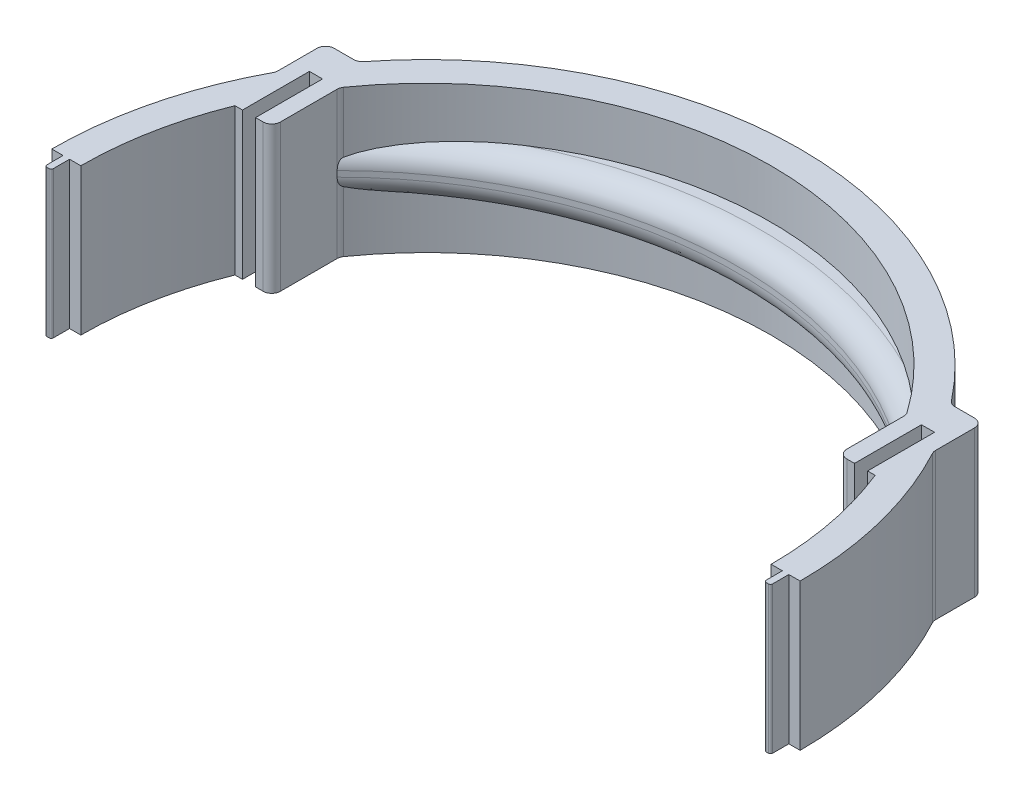
SolidWorks part; units mm, degrees
ref_plane "Front Plane" through (0, 0, 0) normal (0, 0, 1) x (1, 0, 0)
ref_plane "Top Plane" through (0, 0, 0) normal (0, 1, 0) x (1, 0, 0)
ref_plane "Right Plane" through (0, 0, 0) normal (1, 0, 0) x (0, 0, -1)
sketch "Construction Sketch" plane through (0, 0, 0) normal (0, 1, 0) x (1, 0, 0)
  line L0 (-39.5715, 0) -> (39.5715, 0) construction
  line L1 (0, -30.25) -> (0, 30.25) construction
  line L2 (34.71, 22.7218) -> (34.71, 7.2)
  line L3 (-36.21, 22.7218) -> (-34.71, 22.7218)
  line L4 (-36.21, 22.7218) -> (-36.21, 7.2)
  line L5 (-36.21, 7.2) -> (-34.71, 7.2)
  line L6 (-34.71, 22.7218) -> (-34.71, 7.2)
  line L7 (36.21, 7.2) -> (34.71, 7.2)
  line L8 (36.21, 22.7218) -> (36.21, 7.2)
  line L9 (36.21, 22.7218) -> (34.71, 22.7218)
  line L10 (36.21, -22.7218) -> (34.71, -22.7218)
  line L11 (36.21, -22.7218) -> (36.21, -7.2)
  line L12 (36.21, -7.2) -> (34.71, -7.2)
  line L13 (-34.71, -22.7218) -> (-34.71, -7.2)
  line L14 (-36.21, -7.2) -> (-34.71, -7.2)
  line L15 (-36.21, -22.7218) -> (-36.21, -7.2)
  line L16 (-36.21, -22.7218) -> (-34.71, -22.7218)
  line L17 (34.71, -22.7218) -> (34.71, -7.2)
  line L18 (-27.6094, 14.9609) -> (-42.4545, 14.9609) construction
  line L19 (27.6094, 14.9609) -> (42.4545, 14.9609) construction
  line L20 (27.6094, -14.9609) -> (42.4545, -14.9609) construction
  line L21 (-27.6094, -14.9609) -> (-42.4545, -14.9609) construction
  circle A1 centre (0, 0) radius 42.8625
  point P4 (0, 0)
  point P8 (0, 0)
  dimension "D5" = 7.7609
  dimension "D1" = 1.5
  dimension "D2" = 15.5218
  dimension "D3" = 7.2
  dimension "D4" = 34.71
sketch "Sketch3" plane through (0, 0, 0) normal (0, 1, 0) x (1, 0, 0)
  line L0 (-45.7552, 0) -> (45.7552, 0) construction
  line L1 (0, -18.4364) -> (0, 18.4364) construction
  line L2 (34.71, 22.7218) -> (34.71, 14.9609)
  line L3 (-36.23, 22.7218) -> (-34.71, 22.7218)
  line L4 (-36.23, 22.7218) -> (-36.23, 14.9609)
  line L6 (-34.71, 22.7218) -> (-34.71, 14.9609)
  line L8 (36.23, 22.7218) -> (36.23, 14.9609)
  line L9 (36.23, 22.7218) -> (34.71, 22.7218)
  line L10 (36.23, -22.7218) -> (34.71, -22.7218)
  line L11 (36.23, -22.7218) -> (36.23, -14.9609)
  line L13 (-34.71, -22.7218) -> (-34.71, -14.9609)
  line L15 (-36.23, -22.7218) -> (-36.23, -14.9609)
  line L16 (-36.23, -22.7218) -> (-34.71, -22.7218)
  line L17 (34.71, -22.7218) -> (34.71, -14.9609)
  line L18 (-34.8431, 26.4718) -> (-37.105, 26.4718)
  line L19 (-36.23, -14.9609) -> (-37.1022, -14.9609)
  line L21 (36.23, -14.9609) -> (37.1022, -14.9609)
  line L26 (-32.8325, 22.5407) -> (-32.8325, 15.9609)
  line L27 (-42.8625, 33.6264) -> (-42.8625, -34.8883) construction
  line L28 (-33.8325, 14.9609) -> (-34.71, 14.9609)
  line L29 (36.23, 14.9609) -> (37.1022, 14.9609)
  line L31 (-38.105, 25.4718) -> (-38.105, 20.9652)
  line L32 (38.105, 25.4718) -> (38.105, 20.9652)
  line L33 (34.8431, 26.4718) -> (37.105, 26.4718)
  line L34 (33.8325, 14.9609) -> (34.71, 14.9609)
  line L35 (32.8325, 22.5407) -> (32.8325, 15.9609)
  line L36 (38.105, -25.4718) -> (38.105, -20.9652)
  line L37 (34.8431, -26.4718) -> (37.105, -26.4718)
  line L38 (32.8325, -22.5407) -> (32.8325, -15.9609)
  line L39 (33.8325, -14.9609) -> (34.71, -14.9609)
  line L40 (-34.8431, -26.4718) -> (-37.105, -26.4718)
  line L41 (-38.105, -25.4718) -> (-38.105, -20.9652)
  line L42 (-32.8325, -22.5407) -> (-32.8325, -15.9609)
  line L43 (-33.8325, -14.9609) -> (-34.71, -14.9609)
  line L44 (-36.23, 14.9609) -> (-37.1022, 14.9609)
  arc A0 (30.6125, -30.0011) -> (42.8625, 0) centre (0, 0) ccw construction
  arc A1 (-38.2237, 20.4927) -> (-38.2237, -20.4927) centre (0, 0) ccw
  arc A2 (-37.1022, 14.9609) -> (-37.1022, -14.9609) centre (0, 0) ccw
  arc A3 (32.6486, 23.1186) -> (-32.6486, 23.1186) centre (0, 0) ccw
  arc A4 (34.0578, 26.8526) -> (-34.0578, 26.8526) centre (0, 0) ccw
  arc A5 (-32.6486, -23.1186) -> (32.6486, -23.1186) centre (0, 0) ccw
  arc A6 (-34.0578, -26.8526) -> (34.0578, -26.8526) centre (0, 0) ccw
  arc A7 (37.1022, -14.9609) -> (37.1022, 14.9609) centre (0, 0) ccw
  arc A8 (38.2237, -20.4927) -> (38.2237, 20.4927) centre (0, 0) ccw
  arc A9 (-38.105, 20.9652) -> (-38.2237, 20.4927) centre (-39.105, 20.9652) cw
  arc A10 (-34.8431, 26.4718) -> (-34.0578, 26.8526) centre (-34.8431, 27.4718) ccw
  arc A11 (-37.105, 26.4718) -> (-38.105, 25.4718) centre (-37.105, 25.4718) ccw
  arc A12 (-33.8325, 14.9609) -> (-32.8325, 15.9609) centre (-33.8325, 15.9609) ccw
  arc A13 (38.105, 20.9652) -> (38.2237, 20.4927) centre (39.105, 20.9652) ccw
  arc A14 (34.8431, 26.4718) -> (34.0578, 26.8526) centre (34.8431, 27.4718) cw
  arc A15 (-32.6486, -23.1186) -> (-32.8325, -22.5407) centre (-31.8325, -22.5407) cw
  arc A16 (-32.8325, -15.9609) -> (-33.8325, -14.9609) centre (-33.8325, -15.9609) ccw
  arc A17 (-38.105, -20.9652) -> (-38.2237, -20.4927) centre (-39.105, -20.9652) ccw
  arc A18 (-37.105, -26.4718) -> (-38.105, -25.4718) centre (-37.105, -25.4718) cw
  arc A19 (-34.8431, -26.4718) -> (-34.0578, -26.8526) centre (-34.8431, -27.4718) cw
  arc A20 (38.105, -20.9652) -> (38.2237, -20.4927) centre (39.105, -20.9652) cw
  arc A21 (34.8431, -26.4718) -> (34.0578, -26.8526) centre (34.8431, -27.4718) ccw
  arc A22 (32.6486, -23.1186) -> (32.8325, -22.5407) centre (31.8325, -22.5407) ccw
  arc A23 (-32.8325, 22.5407) -> (-32.6486, 23.1186) centre (-31.8325, 22.5407) cw
  arc A24 (38.105, -25.4718) -> (37.105, -26.4718) centre (37.105, -25.4718) cw
  arc A25 (32.8325, -15.9609) -> (33.8325, -14.9609) centre (33.8325, -15.9609) cw
  arc A26 (32.8325, 22.5407) -> (32.6486, 23.1186) centre (31.8325, 22.5407) ccw
  arc A27 (33.8325, 14.9609) -> (32.8325, 15.9609) centre (33.8325, 15.9609) cw
  arc A28 (38.105, 25.4718) -> (37.105, 26.4718) centre (37.105, 25.4718) ccw
  point P3 (0, 0)
  point P6 (0, 0)
  point P54 (-38.105, 20.7125)
  point P57 (-34.3547, 26.4718)
  point P60 (-38.105, 26.4718)
  point P63 (-32.8325, 14.9609)
  point P66 (38.105, 20.7125)
  point P69 (34.3547, 26.4718)
  point P74 (-32.8325, -14.9609)
  point P77 (-38.105, -20.7125)
  point P80 (-38.105, -26.4718)
  point P83 (-34.3547, -26.4718)
  point P86 (38.105, -20.7125)
  point P89 (34.3547, -26.4718)
  point P96 (38.105, -26.4718)
  point P99 (32.8325, -14.9609)
  point P102 (32.8325, 22.8567)
  point P105 (32.8325, 14.9609)
  point P108 (38.105, 26.4718)
  dimension "D3" = 80.01
  dimension "D6" = 7.7609
  dimension "D5" = 86.741
  dimension "D10" = 1
  dimension "D11" = 1
  dimension "D1" = 1.52
  dimension "D2" = 10.03
  dimension "D4" = 34.71
  dimension "D7" = 3.75
  dimension "D8" = 1.875
  dimension "D9" = 8.1525
extrude "Boss-Extrude1" add sketch "Sketch3" along normal blind 5.6667 contours L36 A8 L32 L33 A4 L18 L31 A1 L27 L41 L40 A6 L37 A7 L21 L11 L10 L17 L39 L38 A5 L42 L43 L13 L16 L15 L19 A2 L44 L4 L3 L6 L28 L26 A3 L35 L34 L2 L9 L8 L29
sketch "Sketch4" plane through (0, 5.6667, 0) normal (0, 1, 0) x (1, 0, 0)
  line L0 (-32.8325, 22.5407) -> (-32.8325, 15.9609) construction
  line L1 (-34.71, 22.7218) -> (-34.71, 14.9609) construction
  line L2 (-33.8325, 14.9609) -> (-34.71, 14.9609) construction
  line L3 (-36.23, 22.7218) -> (-34.71, 22.7218) construction
  line L4 (-36.23, 22.7218) -> (-36.23, 14.9609) construction
  line L5 (-36.23, 14.9609) -> (-37.1022, 14.9609) construction
  line L6 (-36.23, -22.7218) -> (-36.23, -14.9609) construction
  line L7 (-36.23, -14.9609) -> (-37.1022, -14.9609) construction
  line L8 (38.105, 20.9652) -> (38.105, 25.4718)
  line L9 (37.105, 26.4718) -> (34.8431, 26.4718)
  line L10 (-34.8431, 26.4718) -> (-37.105, 26.4718)
  line L11 (-38.105, 25.4718) -> (-38.105, 20.9652)
  line L12 (-38.105, -20.9652) -> (-38.105, -25.4718)
  line L13 (-37.105, -26.4718) -> (-34.8431, -26.4718)
  line L14 (34.8431, -26.4718) -> (37.105, -26.4718)
  line L15 (38.105, -25.4718) -> (38.105, -20.9652)
  line L16 (38.105, 20.9652) -> (38.105, 25.4718)
  line L17 (37.105, 26.4718) -> (34.8431, 26.4718)
  line L18 (-34.8431, 26.4718) -> (-37.105, 26.4718)
  line L19 (-38.105, 25.4718) -> (-38.105, 20.9652)
  line L20 (-38.105, -20.9652) -> (-38.105, -25.4718)
  line L21 (-37.105, -26.4718) -> (-34.8431, -26.4718)
  line L22 (34.8431, -26.4718) -> (37.105, -26.4718)
  line L23 (38.105, -25.4718) -> (38.105, -20.9652)
  line L24 (-33.8325, -14.9609) -> (-34.71, -14.9609) construction
  line L25 (-34.71, -22.7218) -> (-34.71, -14.9609) construction
  line L26 (-32.8325, -22.5407) -> (-32.8325, -15.9609) construction
  line L27 (-36.23, -22.7218) -> (-34.71, -22.7218) construction
  line L28 (32.8325, -22.5407) -> (32.8325, -15.9609) construction
  line L29 (34.71, -22.7218) -> (34.71, -14.9609) construction
  line L30 (36.23, -22.7218) -> (34.71, -22.7218) construction
  line L31 (36.23, -22.7218) -> (36.23, -14.9609) construction
  line L32 (33.8325, -14.9609) -> (34.71, -14.9609) construction
  line L33 (36.23, -14.9609) -> (37.1022, -14.9609) construction
  line L34 (36.23, 22.7218) -> (34.71, 22.7218) construction
  line L35 (36.23, 22.7218) -> (36.23, 14.9609) construction
  line L36 (34.71, 22.7218) -> (34.71, 14.9609) construction
  line L37 (32.8325, 22.5407) -> (32.8325, 15.9609) construction
  line L38 (33.8325, 14.9609) -> (34.71, 14.9609) construction
  line L39 (36.23, 14.9609) -> (37.1022, 14.9609) construction
  line L40 (36.23, 14.9609) -> (37.1022, 14.9609)
  line L41 (33.8325, 14.9609) -> (34.71, 14.9609)
  line L42 (32.8325, 22.5407) -> (32.8325, 15.9609)
  line L43 (34.71, 22.7218) -> (34.71, 14.9609)
  line L44 (36.23, 22.7218) -> (36.23, 14.9609)
  line L45 (36.23, 22.7218) -> (34.71, 22.7218)
  line L46 (36.23, -14.9609) -> (37.1022, -14.9609)
  line L47 (33.8325, -14.9609) -> (34.71, -14.9609)
  line L48 (36.23, -22.7218) -> (36.23, -14.9609)
  line L49 (36.23, -22.7218) -> (34.71, -22.7218)
  line L50 (34.71, -22.7218) -> (34.71, -14.9609)
  line L51 (32.8325, -22.5407) -> (32.8325, -15.9609)
  line L52 (-36.23, -22.7218) -> (-34.71, -22.7218)
  line L53 (-32.8325, -22.5407) -> (-32.8325, -15.9609)
  line L54 (-34.71, -22.7218) -> (-34.71, -14.9609)
  line L55 (-33.8325, -14.9609) -> (-34.71, -14.9609)
  line L56 (-36.23, -14.9609) -> (-37.1022, -14.9609)
  line L57 (-36.23, -22.7218) -> (-36.23, -14.9609)
  line L58 (-36.23, 14.9609) -> (-37.1022, 14.9609)
  line L59 (-36.23, 22.7218) -> (-36.23, 14.9609)
  line L60 (-36.23, 22.7218) -> (-34.71, 22.7218)
  line L61 (-33.8325, 14.9609) -> (-34.71, 14.9609)
  line L62 (-34.71, 22.7218) -> (-34.71, 14.9609)
  line L63 (-32.8325, 22.5407) -> (-32.8325, 15.9609)
  arc A1 (32.6486, 23.1186) -> (-32.6486, 23.1186) centre (0, 0) ccw construction
  arc A2 (-32.6486, 23.1186) -> (-32.8325, 22.5407) centre (-31.8325, 22.5407) ccw construction
  arc A3 (-33.8325, 14.9609) -> (-32.8325, 15.9609) centre (-33.8325, 15.9609) ccw construction
  arc A13 (32.8325, 22.5407) -> (32.6486, 23.1186) centre (31.8325, 22.5407) ccw
  arc A14 (32.8325, 15.9609) -> (33.8325, 14.9609) centre (33.8325, 15.9609) ccw
  arc A15 (37.1022, -14.9609) -> (37.1022, 14.9609) centre (0, 0) ccw
  arc A16 (38.105, 25.4718) -> (37.105, 26.4718) centre (37.105, 25.4718) ccw
  arc A17 (34.0578, 26.8526) -> (34.8431, 26.4718) centre (34.8431, 27.4718) ccw
  arc A18 (34.0578, 26.8526) -> (-34.0578, 26.8526) centre (0, 0) ccw
  arc A19 (-34.8431, 26.4718) -> (-34.0578, 26.8526) centre (-34.8431, 27.4718) ccw
  arc A20 (-37.105, 26.4718) -> (-38.105, 25.4718) centre (-37.105, 25.4718) ccw
  arc A21 (-38.2237, 20.4927) -> (-38.105, 20.9652) centre (-39.105, 20.9652) ccw
  arc A22 (-38.2237, 20.4927) -> (-38.2237, -20.4927) centre (0, 0) ccw
  arc A23 (-38.105, -20.9652) -> (-38.2237, -20.4927) centre (-39.105, -20.9652) ccw
  arc A24 (-38.105, -25.4718) -> (-37.105, -26.4718) centre (-37.105, -25.4718) ccw
  arc A25 (-34.0578, -26.8526) -> (-34.8431, -26.4718) centre (-34.8431, -27.4718) ccw
  arc A26 (-34.0578, -26.8526) -> (34.0578, -26.8526) centre (0, 0) ccw
  arc A27 (34.8431, -26.4718) -> (34.0578, -26.8526) centre (34.8431, -27.4718) ccw
  arc A28 (37.105, -26.4718) -> (38.105, -25.4718) centre (37.105, -25.4718) ccw
  arc A29 (38.2237, -20.4927) -> (38.105, -20.9652) centre (39.105, -20.9652) ccw
  arc A30 (38.2237, -20.4927) -> (38.2237, 20.4927) centre (0, 0) ccw
  arc A31 (38.105, 20.9652) -> (38.2237, 20.4927) centre (39.105, 20.9652) ccw
  arc A32 (38.105, 25.4718) -> (37.105, 26.4718) centre (37.105, 25.4718) ccw
  arc A33 (34.0578, 26.8526) -> (34.8431, 26.4718) centre (34.8431, 27.4718) ccw
  arc A34 (34.0578, 26.8526) -> (-34.0578, 26.8526) centre (0, 0) ccw
  arc A35 (-34.8431, 26.4718) -> (-34.0578, 26.8526) centre (-34.8431, 27.4718) ccw
  arc A36 (-37.105, 26.4718) -> (-38.105, 25.4718) centre (-37.105, 25.4718) ccw
  arc A37 (-38.2237, 20.4927) -> (-38.105, 20.9652) centre (-39.105, 20.9652) ccw
  arc A38 (-38.2237, 20.4927) -> (-38.2237, -20.4927) centre (0, 0) ccw
  arc A39 (-38.105, -20.9652) -> (-38.2237, -20.4927) centre (-39.105, -20.9652) ccw
  arc A40 (-38.105, -25.4718) -> (-37.105, -26.4718) centre (-37.105, -25.4718) ccw
  arc A41 (-34.0578, -26.8526) -> (-34.8431, -26.4718) centre (-34.8431, -27.4718) ccw
  arc A42 (-34.0578, -26.8526) -> (34.0578, -26.8526) centre (0, 0) ccw
  arc A43 (34.8431, -26.4718) -> (34.0578, -26.8526) centre (34.8431, -27.4718) ccw
  arc A44 (37.105, -26.4718) -> (38.105, -25.4718) centre (37.105, -25.4718) ccw
  arc A45 (38.2237, -20.4927) -> (38.105, -20.9652) centre (39.105, -20.9652) ccw
  arc A46 (38.2237, -20.4927) -> (38.2237, 20.4927) centre (0, 0) ccw
  arc A47 (38.105, 20.9652) -> (38.2237, 20.4927) centre (39.105, 20.9652) ccw
  arc A48 (33.8325, -14.9609) -> (32.8325, -15.9609) centre (33.8325, -15.9609) ccw
  arc A49 (32.6486, -23.1186) -> (32.8325, -22.5407) centre (31.8325, -22.5407) ccw
  arc A50 (-32.6486, -23.1186) -> (32.6486, -23.1186) centre (0, 0) ccw
  arc A51 (-32.8325, -22.5407) -> (-32.6486, -23.1186) centre (-31.8325, -22.5407) ccw
  arc A52 (-32.8325, -15.9609) -> (-33.8325, -14.9609) centre (-33.8325, -15.9609) ccw
  arc A53 (-37.1022, 14.9609) -> (-37.1022, -14.9609) centre (0, 0) ccw
  arc A54 (-33.8325, 14.9609) -> (-32.8325, 15.9609) centre (-33.8325, 15.9609) ccw
  arc A55 (-32.6486, 23.1186) -> (-32.8325, 22.5407) centre (-31.8325, 22.5407) ccw
  arc A56 (32.6486, 23.1186) -> (-32.6486, 23.1186) centre (0, 0) ccw
  dimension "D1" = 0
ref_plane "Plane1" through (0, 11.3333, 0) normal (0, 1, 0) x (1, 0, 0)
sketch "Sketch5" plane through (0, 11.3333, 0) normal (0, 1, 0) x (1, 0, 0)
  line L0 (38.105, 20.9652) -> (38.105, 25.4718)
  line L1 (37.105, 26.4718) -> (34.8431, 26.4718)
  line L2 (-34.8431, 26.4718) -> (-37.105, 26.4718)
  line L3 (-38.105, 25.4718) -> (-38.105, 20.9652)
  line L4 (-38.105, -20.9652) -> (-38.105, -25.4718)
  line L5 (-37.105, -26.4718) -> (-34.8431, -26.4718)
  line L6 (34.8431, -26.4718) -> (37.105, -26.4718)
  line L7 (38.105, -25.4718) -> (38.105, -20.9652)
  line L8 (36.23, 14.9609) -> (37.1022, 14.9609)
  line L9 (33.8325, 14.9609) -> (34.71, 14.9609)
  line L10 (32.8325, 22.5407) -> (32.8325, 15.9609)
  line L11 (34.71, 22.7218) -> (34.71, 14.9609)
  line L12 (36.23, 22.7218) -> (36.23, 14.9609)
  line L13 (36.23, 22.7218) -> (34.71, 22.7218)
  line L14 (36.23, -14.9609) -> (37.1022, -14.9609)
  line L15 (33.8325, -14.9609) -> (34.71, -14.9609)
  line L16 (36.23, -22.7218) -> (36.23, -14.9609)
  line L17 (36.23, -22.7218) -> (34.71, -22.7218)
  line L18 (34.71, -22.7218) -> (34.71, -14.9609)
  line L19 (32.8325, -22.5407) -> (32.8325, -15.9609)
  line L20 (-36.23, -22.7218) -> (-34.71, -22.7218)
  line L21 (-32.8325, -22.5407) -> (-32.8325, -15.9609)
  line L22 (-34.71, -22.7218) -> (-34.71, -14.9609)
  line L23 (-33.8325, -14.9609) -> (-34.71, -14.9609)
  line L24 (-36.23, -14.9609) -> (-37.1022, -14.9609)
  line L25 (-36.23, -22.7218) -> (-36.23, -14.9609)
  line L26 (-36.23, 14.9609) -> (-37.1022, 14.9609)
  line L27 (-36.23, 22.7218) -> (-36.23, 14.9609)
  line L28 (-36.23, 22.7218) -> (-34.71, 22.7218)
  line L29 (-33.8325, 14.9609) -> (-34.71, 14.9609)
  line L30 (-34.71, 22.7218) -> (-34.71, 14.9609)
  line L31 (-32.8325, 22.5407) -> (-32.8325, 15.9609)
  line L32 (-76.2008, 0) -> (76.2008, 0) construction
  arc A1 (32.8325, 15.9609) -> (33.8325, 14.9609) centre (33.8325, 15.9609) ccw
  arc A2 (37.1022, -14.9609) -> (37.1022, 14.9609) centre (0, 0) ccw
  arc A3 (38.105, 25.4718) -> (37.105, 26.4718) centre (37.105, 25.4718) ccw
  arc A7 (-37.105, 26.4718) -> (-38.105, 25.4718) centre (-37.105, 25.4718) ccw
  arc A8 (-38.2237, 20.4927) -> (-38.105, 20.9652) centre (-39.105, 20.9652) ccw
  arc A9 (-38.2237, 20.4927) -> (-38.2237, -20.4927) centre (0, 0) ccw
  arc A10 (-38.105, -20.9652) -> (-38.2237, -20.4927) centre (-39.105, -20.9652) ccw
  arc A11 (-38.105, -25.4718) -> (-37.105, -26.4718) centre (-37.105, -25.4718) ccw
  arc A15 (37.105, -26.4718) -> (38.105, -25.4718) centre (37.105, -25.4718) ccw
  arc A16 (38.2237, -20.4927) -> (38.105, -20.9652) centre (39.105, -20.9652) ccw
  arc A17 (38.2237, -20.4927) -> (38.2237, 20.4927) centre (0, 0) ccw
  arc A18 (38.105, 20.9652) -> (38.2237, 20.4927) centre (39.105, 20.9652) ccw
  arc A19 (33.8325, -14.9609) -> (32.8325, -15.9609) centre (33.8325, -15.9609) ccw
  arc A23 (-32.8325, -15.9609) -> (-33.8325, -14.9609) centre (-33.8325, -15.9609) ccw
  arc A24 (-37.1022, 14.9609) -> (-37.1022, -14.9609) centre (0, 0) ccw
  arc A25 (-33.8325, 14.9609) -> (-32.8325, 15.9609) centre (-33.8325, 15.9609) ccw
  arc A28 (-32.8325, 22.5407) -> (32.8325, 22.5407) centre (0, -10.2918) cw
  arc A29 (-32.8325, -22.5407) -> (32.8325, -22.5407) centre (0, 10.2918) ccw
  arc A30 (-34.8431, 26.4718) -> (34.8431, 26.4718) centre (0, -8.3713) cw
  arc A31 (-34.8431, -26.4718) -> (34.8431, -26.4718) centre (0, 8.3713) ccw
  point P87 (0, 0)
extrude "Boss-Extrude3" add sketch "Sketch5" against normal blind 5.6667
sketch "Sketch7" plane through (0, 11.3333, 0) normal (0, 1, 0) x (1, 0, 0)
  line L0 (38.105, 20.9652) -> (38.105, 25.4718)
  line L1 (37.105, 26.4718) -> (34.8431, 26.4718)
  line L2 (-34.8431, 26.4718) -> (-37.105, 26.4718)
  line L3 (-38.105, 25.4718) -> (-38.105, 20.9652)
  line L4 (-38.105, -20.9652) -> (-38.105, -25.4718)
  line L5 (-37.105, -26.4718) -> (-34.8431, -26.4718)
  line L6 (34.8431, -26.4718) -> (37.105, -26.4718)
  line L7 (38.105, -25.4718) -> (38.105, -20.9652)
  line L8 (36.23, 14.9609) -> (37.1022, 14.9609)
  line L9 (33.8325, 14.9609) -> (34.71, 14.9609)
  line L10 (32.8325, 22.5407) -> (32.8325, 15.9609)
  line L11 (34.71, 22.7218) -> (34.71, 14.9609)
  line L12 (36.23, 22.7218) -> (36.23, 14.9609)
  line L13 (36.23, 22.7218) -> (34.71, 22.7218)
  line L14 (36.23, -14.9609) -> (37.1022, -14.9609)
  line L15 (33.8325, -14.9609) -> (34.71, -14.9609)
  line L16 (36.23, -22.7218) -> (36.23, -14.9609)
  line L17 (36.23, -22.7218) -> (34.71, -22.7218)
  line L18 (34.71, -22.7218) -> (34.71, -14.9609)
  line L19 (32.8325, -22.5407) -> (32.8325, -15.9609)
  line L20 (-36.23, -22.7218) -> (-34.71, -22.7218)
  line L21 (-32.8325, -22.5407) -> (-32.8325, -15.9609)
  line L22 (-34.71, -22.7218) -> (-34.71, -14.9609)
  line L23 (-33.8325, -14.9609) -> (-34.71, -14.9609)
  line L24 (-36.23, -14.9609) -> (-37.1022, -14.9609)
  line L25 (-36.23, -22.7218) -> (-36.23, -14.9609)
  line L26 (-36.23, 14.9609) -> (-37.1022, 14.9609)
  line L27 (-36.23, 22.7218) -> (-36.23, 14.9609)
  line L28 (-36.23, 22.7218) -> (-34.71, 22.7218)
  line L29 (-33.8325, 14.9609) -> (-34.71, 14.9609)
  line L30 (-34.71, 22.7218) -> (-34.71, 14.9609)
  line L31 (-32.8325, 22.5407) -> (-32.8325, 15.9609)
  arc A0 (32.8325, 22.5407) -> (32.6486, 23.1186) centre (31.8325, 22.5407) ccw
  arc A1 (32.8325, 15.9609) -> (33.8325, 14.9609) centre (33.8325, 15.9609) ccw
  arc A2 (37.1022, -14.9609) -> (37.1022, 14.9609) centre (0, 0) ccw
  arc A3 (38.105, 25.4718) -> (37.105, 26.4718) centre (37.105, 25.4718) ccw
  arc A4 (34.0578, 26.8526) -> (34.8431, 26.4718) centre (34.8431, 27.4718) ccw
  arc A5 (34.0578, 26.8526) -> (-34.0578, 26.8526) centre (0, 0) ccw
  arc A6 (-34.8431, 26.4718) -> (-34.0578, 26.8526) centre (-34.8431, 27.4718) ccw
  arc A7 (-37.105, 26.4718) -> (-38.105, 25.4718) centre (-37.105, 25.4718) ccw
  arc A8 (-38.2237, 20.4927) -> (-38.105, 20.9652) centre (-39.105, 20.9652) ccw
  arc A9 (-38.2237, 20.4927) -> (-38.2237, -20.4927) centre (0, 0) ccw
  arc A10 (-38.105, -20.9652) -> (-38.2237, -20.4927) centre (-39.105, -20.9652) ccw
  arc A11 (-38.105, -25.4718) -> (-37.105, -26.4718) centre (-37.105, -25.4718) ccw
  arc A12 (-34.0578, -26.8526) -> (-34.8431, -26.4718) centre (-34.8431, -27.4718) ccw
  arc A13 (-34.0578, -26.8526) -> (34.0578, -26.8526) centre (0, 0) ccw
  arc A14 (34.8431, -26.4718) -> (34.0578, -26.8526) centre (34.8431, -27.4718) ccw
  arc A15 (37.105, -26.4718) -> (38.105, -25.4718) centre (37.105, -25.4718) ccw
  arc A16 (38.2237, -20.4927) -> (38.105, -20.9652) centre (39.105, -20.9652) ccw
  arc A17 (38.2237, -20.4927) -> (38.2237, 20.4927) centre (0, 0) ccw
  arc A18 (38.105, 20.9652) -> (38.2237, 20.4927) centre (39.105, 20.9652) ccw
  arc A19 (33.8325, -14.9609) -> (32.8325, -15.9609) centre (33.8325, -15.9609) ccw
  arc A20 (32.6486, -23.1186) -> (32.8325, -22.5407) centre (31.8325, -22.5407) ccw
  arc A21 (-32.6486, -23.1186) -> (32.6486, -23.1186) centre (0, 0) ccw
  arc A22 (-32.8325, -22.5407) -> (-32.6486, -23.1186) centre (-31.8325, -22.5407) ccw
  arc A23 (-32.8325, -15.9609) -> (-33.8325, -14.9609) centre (-33.8325, -15.9609) ccw
  arc A24 (-37.1022, 14.9609) -> (-37.1022, -14.9609) centre (0, 0) ccw
  arc A25 (-33.8325, 14.9609) -> (-32.8325, 15.9609) centre (-33.8325, 15.9609) ccw
  arc A26 (-32.6486, 23.1186) -> (-32.8325, 22.5407) centre (-31.8325, 22.5407) ccw
  arc A27 (32.6486, 23.1186) -> (-32.6486, 23.1186) centre (0, 0) ccw
extrude "Boss-Extrude4" add sketch "Sketch7" along normal blind 5.6667
fillet "Fillet1" radius 2.5 8 edges at (0, 5.6667, -40.9043) (0, 11.3333, -40.9043) (0, 5.6667, -36.1403) (0, 11.3333, -36.1403) (0, 5.6667, 40.9043) (0, 11.3333, 40.9043) (0, 5.6667, 36.1403) (0, 11.3333, 36.1403)
sketch "Sketch8" plane through (0, 17, 0) normal (0, 1, 0) x (1, 0, 0)
  line L0 (-63.4296, 0) -> (-42.0628, 0) construction
  line L1 (36.23, -22.7218) -> (34.71, -22.7218) construction
  line L2 (32.8325, -22.5407) -> (32.8325, -15.9609) construction
  line L3 (34.71, -22.7218) -> (34.71, -14.9609) construction
  line L6 (36.23, -22.7218) -> (36.23, -14.9609) construction
  line L8 (38.105, 20.9652) -> (38.105, 25.4718)
  line L9 (37.105, 26.4718) -> (34.8431, 26.4718)
  line L10 (-34.8431, 26.4718) -> (-37.105, 26.4718)
  line L11 (-38.105, 25.4718) -> (-38.105, 20.9652)
  line L12 (-38.105, -20.9652) -> (-38.105, -25.4718)
  line L13 (-37.105, -26.4718) -> (-34.8431, -26.4718)
  line L14 (34.8431, -26.4718) -> (37.105, -26.4718)
  line L15 (38.105, -25.4718) -> (38.105, -20.9652)
  line L20 (-38.105, -20.9652) -> (-38.105, -25.4718)
  line L21 (-37.105, -26.4718) -> (-34.8431, -26.4718)
  line L22 (34.8431, -26.4718) -> (37.105, -26.4718)
  line L23 (38.105, -25.4718) -> (38.105, -20.9652)
  line L29 (-36.23, -22.7218) -> (-34.71, -22.7218) construction
  line L30 (-32.8325, -22.5407) -> (-32.8325, -15.9609) construction
  line L32 (-34.71, -22.7218) -> (-34.71, -14.9609) construction
  line L33 (-36.23, -22.7218) -> (-36.23, -14.9609) construction
  line L41 (36.23, -22.7218) -> (34.71, -22.7218)
  line L42 (32.8325, -22.5407) -> (32.8325, -15.9609)
  line L43 (34.71, -22.7218) -> (34.71, -14.9609)
  line L44 (33.8325, -14.9609) -> (34.71, -14.9609)
  line L45 (36.23, -14.9609) -> (37.1022, -14.9609)
  line L46 (36.23, -22.7218) -> (36.23, -14.9609)
  line L53 (-36.23, -22.7218) -> (-34.71, -22.7218)
  line L54 (-32.8325, -22.5407) -> (-32.8325, -15.9609)
  line L55 (-33.8325, -14.9609) -> (-34.71, -14.9609)
  line L56 (-34.71, -22.7218) -> (-34.71, -14.9609)
  line L57 (-36.23, -22.7218) -> (-36.23, -14.9609)
  line L58 (-36.23, -14.9609) -> (-37.1022, -14.9609)
  line L65 (43.3705, 0) -> (42.0628, 0)
  line L66 (43.3705, -8.215) -> (43.3705, 0) construction
  line L67 (40.005, -8.215) -> (40.005, 0) construction
  line L68 (0, -51.8966) -> (0, -40.005) construction
  line L70 (41.3128, 0) -> (41.3128, -2.125)
  line L71 (41.3128, -2.125) -> (42.0628, -2.125)
  line L72 (42.0628, 0) -> (42.0628, -2.125)
  line L73 (-40.005, 0) -> (-41.3128, 0)
  line L74 (40.005, 0) -> (41.3128, 0) construction
  line L77 (-40.005, -8.215) -> (-40.005, 0) construction
  line L78 (-43.3705, -8.215) -> (-43.3705, 0) construction
  line L79 (-42.0628, 0) -> (-42.0628, -2.125)
  line L80 (-41.3128, -2.125) -> (-42.0628, -2.125)
  line L81 (-41.3128, 0) -> (-41.3128, -2.125)
  line L83 (41.3128, 0) -> (40.005, 0)
  line L84 (42.0628, 0) -> (63.4296, 0) construction
  line L86 (-42.0628, 0) -> (-43.3705, 0)
  line L87 (-41.3128, 0) -> (-40.005, 0) construction
  arc A1 (32.6486, -23.1186) -> (32.8325, -22.5407) centre (31.8325, -22.5407) ccw construction
  arc A2 (33.8325, -14.9609) -> (32.8325, -15.9609) centre (33.8325, -15.9609) ccw construction
  arc A6 (-32.8325, -22.5407) -> (-32.6486, -23.1186) centre (-31.8325, -22.5407) ccw construction
  arc A8 (-32.8325, -15.9609) -> (-33.8325, -14.9609) centre (-33.8325, -15.9609) ccw construction
  arc A13 (32.6486, -23.1186) -> (32.8325, -22.5407) centre (31.8325, -22.5407) ccw
  arc A14 (33.8325, -14.9609) -> (32.8325, -15.9609) centre (33.8325, -15.9609) ccw
  arc A15 (37.1022, -14.9609) -> (40.005, 0) centre (0, 0) ccw
  arc A16 (38.105, 20.9652) -> (38.2237, 20.4927) centre (39.105, 20.9652) ccw
  arc A17 (38.105, 25.4718) -> (37.105, 26.4718) centre (37.105, 25.4718) ccw
  arc A18 (34.0578, 26.8526) -> (34.8431, 26.4718) centre (34.8431, 27.4718) ccw
  arc A19 (34.0578, 26.8526) -> (-34.0578, 26.8526) centre (0, 0) ccw
  arc A20 (-34.8431, 26.4718) -> (-34.0578, 26.8526) centre (-34.8431, 27.4718) ccw
  arc A21 (-37.105, 26.4718) -> (-38.105, 25.4718) centre (-37.105, 25.4718) ccw
  arc A22 (-38.2237, 20.4927) -> (-38.105, 20.9652) centre (-39.105, 20.9652) ccw
  arc A23 (-38.2237, 20.4927) -> (-38.2237, -20.4927) centre (0, 0) ccw
  arc A24 (-38.105, -20.9652) -> (-38.2237, -20.4927) centre (-39.105, -20.9652) ccw
  arc A25 (-38.105, -25.4718) -> (-37.105, -26.4718) centre (-37.105, -25.4718) ccw
  arc A26 (-34.0578, -26.8526) -> (-34.8431, -26.4718) centre (-34.8431, -27.4718) ccw
  arc A27 (-34.0578, -26.8526) -> (34.0578, -26.8526) centre (0, 0) ccw
  arc A28 (34.8431, -26.4718) -> (34.0578, -26.8526) centre (34.8431, -27.4718) ccw
  arc A29 (37.105, -26.4718) -> (38.105, -25.4718) centre (37.105, -25.4718) ccw
  arc A30 (38.2237, -20.4927) -> (38.105, -20.9652) centre (39.105, -20.9652) ccw
  arc A31 (38.2237, -20.4927) -> (38.2237, 20.4927) centre (0, 0) ccw
  arc A39 (-43.3705, 0) -> (-38.2237, -20.4927) centre (0, 0) ccw
  arc A40 (-38.105, -20.9652) -> (-38.2237, -20.4927) centre (-39.105, -20.9652) ccw
  arc A41 (-38.105, -25.4718) -> (-37.105, -26.4718) centre (-37.105, -25.4718) ccw
  arc A42 (-34.0578, -26.8526) -> (-34.8431, -26.4718) centre (-34.8431, -27.4718) ccw
  arc A43 (-34.0578, -26.8526) -> (34.0578, -26.8526) centre (0, 0) ccw
  arc A44 (34.8431, -26.4718) -> (34.0578, -26.8526) centre (34.8431, -27.4718) ccw
  arc A45 (37.105, -26.4718) -> (38.105, -25.4718) centre (37.105, -25.4718) ccw
  arc A46 (38.2237, -20.4927) -> (38.105, -20.9652) centre (39.105, -20.9652) ccw
  arc A47 (38.2237, -20.4927) -> (43.3705, 0) centre (0, 0) ccw
  arc A50 (-32.8325, -22.5407) -> (-32.6486, -23.1186) centre (-31.8325, -22.5407) ccw
  arc A51 (-32.6486, -23.1186) -> (32.6486, -23.1186) centre (0, 0) ccw
  arc A52 (-32.8325, -15.9609) -> (-33.8325, -14.9609) centre (-33.8325, -15.9609) ccw
  arc A53 (-40.005, 0) -> (-37.1022, -14.9609) centre (0, 0) ccw
  arc A57 (-43.3705, 0) -> (43.3705, 0) centre (0, 0) ccw construction
  arc A58 (-32.8325, -22.5407) -> (32.8325, -22.5407) centre (0, 10.2918) ccw construction
  arc A59 (-32.8325, -22.5407) -> (32.8325, -22.5407) centre (0, 10.2918) ccw
  point P13 (0, 0)
  point P90 (41.6878, 0)
  point P93 (43.3705, 0)
  point P96 (40.005, 0)
  point P104 (0, 0)
  point P112 (-40.005, 0)
  point P113 (-43.3705, 0)
  point P114 (-41.6878, 0)
  dimension "D3" = 3.3655
  dimension "D1" = 0
extrude "Cut-Extrude1" cut sketch "Sketch8" against normal through all contours A53 L73 L81 L80 L79 L86 A39 A40 L20 A41 L21 A42 A43 A44 L22 A45 L23 A46 A47 L65 L72 L71 L70 L83 A15 L45 L46 L41 L43 L44 A14 L42 A13 A51 A50 L54 A52 L55 L56 L53 L57 L58
sketch "Sketch9" plane through (0, 17, 0) normal (0, 1, 0) x (1, 0, 0)
  line L1 (-45.8383, -44.1815) -> (47.127, -44.1815)
  line L2 (-45.8383, -44.1815) -> (-45.8383, -14.1749)
  line L3 (-45.8383, -14.1749) -> (47.127, -14.1749)
  line L4 (47.127, -44.1815) -> (47.127, -14.1749)
extrude "Cut-Extrude2" cut sketch "Sketch9" against normal through all
fillet "Fillet2" radius 0.25 4 edges at (41.3128, 8.5, 2.125) (42.0628, 8.5, 2.125) (-41.3128, 8.5, 2.125) (-42.0628, 8.5, 2.125)
